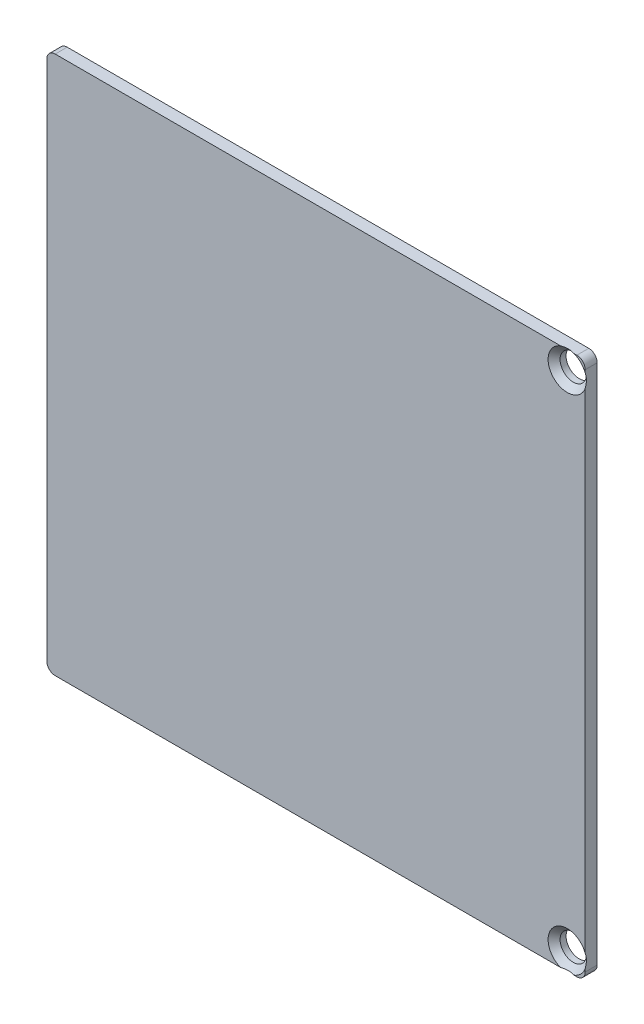
SolidWorks part; units mm, degrees
ref_plane "前视基准面" through (0, 0, 0) normal (0, 0, 1) x (1, 0, 0)
ref_plane "上视基准面" through (0, 0, 0) normal (0, 1, 0) x (1, 0, 0)
ref_plane "右视基准面" through (0, 0, 0) normal (1, 0, 0) x (0, 0, -1)
sketch "草图1" plane through (0, 0, 0) normal (0, 0, 1) x (1, 0, 0)
  line L32 (22.5, -21.8) -> (22.5, 21.8)
  line L33 (-21.8, -22.5) -> (21.8, -22.5)
  line L34 (-22.5, 21.8) -> (-22.5, -21.8)
  line L35 (21.8, 22.5) -> (-21.8, 22.5)
  line L36 (22.5, -21.8) -> (22.5, 21.8)
  line L37 (-21.8, -22.5) -> (21.8, -22.5)
  line L38 (-22.5, 21.8) -> (-22.5, -21.8)
  line L39 (21.8, 22.5) -> (-21.8, 22.5)
  arc A20 (22.5, 21.8) -> (21.8, 22.5) centre (21.8, 21.8) ccw
  arc A21 (21.8, -22.5) -> (22.5, -21.8) centre (21.8, -21.8) ccw
  arc A22 (-22.5, -21.8) -> (-21.8, -22.5) centre (-21.8, -21.8) ccw
  arc A23 (-21.8, 22.5) -> (-22.5, 21.8) centre (-21.8, 21.8) ccw
  arc A24 (22.5, 21.8) -> (21.8, 22.5) centre (21.8, 21.8) ccw
  arc A25 (21.8, -22.5) -> (22.5, -21.8) centre (21.8, -21.8) ccw
  arc A26 (-22.5, -21.8) -> (-21.8, -22.5) centre (-21.8, -21.8) ccw
  arc A27 (-21.8, 22.5) -> (-22.5, 21.8) centre (-21.8, 21.8) ccw
  dimension "D1" = 0.3
extrude "凸台-拉伸1" add sketch "草图1" along normal blind 1
sketch "草图2" plane through (0, 0, 0) normal (0, 0, -1) x (-1, 0, 0)
  line L0 (22.5, 21.8) -> (22.5, -21.8) construction
  line L1 (22.5, 14.5) -> (20.5, 14.5)
  line L2 (22.5, 14.5) -> (22.5, -14.5)
  line L3 (22.5, -14.5) -> (20.5, -14.5)
  line L4 (20.5, 14.5) -> (20.5, -14.5)
  line L5 (21.8, -22.5) -> (-21.8, -22.5) construction
  line L6 (-21.8, 22.5) -> (21.8, 22.5) construction
  dimension "D1" = 2
  dimension "D2" = 8
  dimension "D3" = 8
extrude "凸台-拉伸2" add sketch "草图2" along normal blind 7
sketch "草图3" plane through (0, 0, 0) normal (0, 0, -1) x (-1, 0, 0)
  circle A2 centre (-21, 21) radius 1.1
  circle A3 centre (-21, 21) radius 1.1
  circle A5 centre (-21, -21) radius 1.1
  circle A6 centre (-21, -21) radius 1.1
  dimension "D1" = 0.3
  dimension "D2" = 0.3
extrude "切除-拉伸1" cut sketch "草图3" against normal blind 7
sketch "草图4" plane through (-22.5, 0, 0) normal (-1, 0, 0) x (0, 0, 1)
  circle A0 centre (-3.5, 10) radius 0.8
  circle A1 centre (-3.5, -10) radius 0.8
  dimension "D1" = 1.6
  dimension "D2" = 1.6
extrude "切除-拉伸2" cut sketch "草图4" against normal blind 7
chamfer "倒角1" distance 0.5 distance2 0.5 2 edges at (22.1, 21, 1) (22.1, -21, 1)
fillet "圆角1" radius 4 2 edges at (-21.5, 14.5, -7) (-21.5, -14.5, -7)
sketch "草图5" plane through (-22.5, 0, 0) normal (-1, 0, 0) x (0, 0, 1)
  line L0 (1, 21.8) -> (1, -21.8) construction
  line L1 (-4.5, 5) -> (-1.5, 5)
  line L2 (-5.5, 4) -> (-5.5, -4)
  line L3 (-4.5, -5) -> (-1.5, -5)
  line L4 (-0.5, 4) -> (-0.5, -4)
  line L5 (-5.5, 5) -> (-0.5, -5) construction
  line L6 (-5.5, -5) -> (-0.5, 5) construction
  arc A0 (-1.5, 5) -> (-0.5, 4) centre (-1.5, 4) cw
  arc A1 (-5.5, -4) -> (-4.5, -5) centre (-4.5, -4) ccw
  arc A2 (-4.5, 5) -> (-5.5, 4) centre (-4.5, 4) ccw
  arc A3 (-1.5, -5) -> (-0.5, -4) centre (-1.5, -4) ccw
  point P0 (-3, 0)
  point P7 (0, 0)
  dimension "D4" = 1
  dimension "D1" = 1.5
  dimension "D2" = 5
  dimension "D3" = 10
extrude "切除-拉伸3" cut sketch "草图5" against normal blind 10
